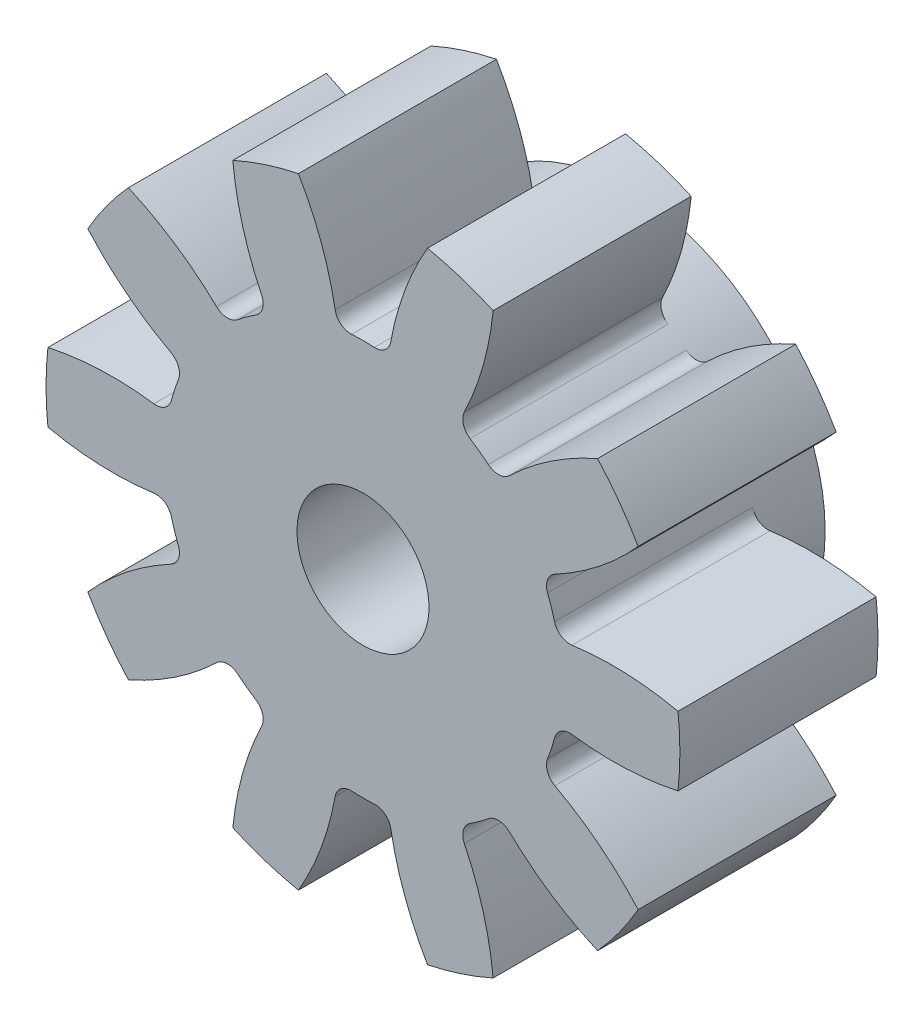
SolidWorks part; units mm, degrees
ref_plane "Front Plane" through (0, 0, 0) normal (0, 0, 1) x (1, 0, 0)
ref_plane "Top Plane" through (0, 0, 0) normal (0, 1, 0) x (1, 0, 0)
ref_plane "Right Plane" through (0, 0, 0) normal (1, 0, 0) x (0, 0, -1)
sketch "Sketch1" plane through (0, 0, 0) normal (0, 0, 1) x (1, 0, 0)
  circle A0 centre (0, 0) radius 10
  circle A1 centre (0, 0) radius 12
  circle A2 centre (0, 0) radius 7.5
  dimension "D1" = 20
  dimension "D2" = 24
  dimension "D3" = 4.5
extrude "Boss-Extrude1" add sketch "Sketch1" along normal mid plane 425 contours A1
sketch "Sketch2" plane through (0, 0, 0) normal (0, 0, 1) x (1, 0, 0)
  line L0 (0, 0) -> (0, 12) construction
  line L1 (-1.5643, 9.8769) -> (1.5643, 9.8769) construction
  line L2 (-0.9691, 7.4371) -> (0, 0) construction
  line L3 (0, 5.5789) -> (-2.6051, 12.7363) construction
  line L4 (0, 0) -> (3.7082, 11.4127) construction
  line L5 (1.5643, 9.8769) -> (4.5399, 8.9101) construction
  circle A0 centre (0, 0) radius 12 construction
  arc A1 (-3.0254, 12.6431) -> (-0.9691, 7.4371) centre (-12.3373, 5.9558) cw
  arc A2 (3.0254, 12.6431) -> (0.9691, 7.4371) centre (12.3373, 5.9558) ccw
  circle A3 centre (0, 0) radius 7.5 construction
  arc A4 (0.9691, 7.4371) -> (-0.9691, 7.4371) centre (0, 0) ccw
  circle A5 centre (0, 0) radius 12 construction
  circle A6 centre (0, 0) radius 10 construction
  circle A7 centre (0, 0) radius 13
  arc A8 (3.0254, 12.6431) -> (-3.0254, 12.6431) centre (0, 0) ccw
  dimension "D2" = 1.9081
  dimension "D3" = 20
  dimension "D4" = 18
extrude "Cut-Extrude1" cut sketch "Sketch2" against normal through all both and the other way through all
fillet "Fillet1" radius 0.6 1 edges at (-0.9691, 7.4371, 0) type face fillet first side face at (-1.5984, 9.6298, 0) second side face at (0, 7.4686, 0)
fillet "Fillet2" radius 0.6 1 edges at (0.9691, 7.4371, 0) type face fillet first side face at (1.5984, 9.6298, 0) second side face at (0.2709, 7.4788, 0)
sketch "Sketch3" plane through (0, 0, -212.5) normal (0, 0, -1) x (-1, 0, 0)
pattern_circular "CirPattern2" count 10 over 360 about axis through (0, 0, 212.5) along (0, 0, 1) of "Cut-Extrude1", "Fillet1", "Fillet2"
sketch "Sketch4" plane through (0, 0, -212.5) normal (0, 0, -1) x (-1, 0, 0)
  circle A0 centre (0, 0) radius 7.5
  circle A1 centre (0, 0) radius 2.5
  dimension "D1" = 5
extrude "Boss-Extrude2" add sketch "Sketch4" along normal mid plane 5 contours A0 | A1
sketch "Sketch5" plane through (0, 0, -212.5) normal (0, 0, -1) x (-1, 0, 0)
  circle A0 centre (0, 0) radius 3
extrude "Cut-Extrude2" cut sketch "Sketch5" against normal blind 32 and the other way through all
sketch "Sketch6" plane through (0, 0, 212.5) normal (0, 0, 1) x (1, 0, 0)
  circle A0 centre (0, 0) radius 7.5
  dimension "D1" = 15
extrude "Boss-Extrude3" add sketch "Sketch6" along normal mid plane 12
ref_plane "Plane1" through (0, 0, -205) normal (0, 0, -1) x (-1, 0, 0)
sketch "Sketch7" plane through (0, 0, 218.5) normal (0, 0, 1) x (1, 0, 0)
  circle A0 centre (0, 0) radius 12
extrude "Cut-Extrude3" cut sketch "Sketch7" against normal up to surface (423.5 mm away) contours A0 up to plane "Plane1"
sketch "Sketch8" plane through (0, 0, -215) normal (0, 0, -1) x (-1, 0, 0)
  circle A0 centre (0, 0) radius 1.65
  circle A1 centre (0, 0) radius 7.5
  dimension "D1" = 3.3
extrude "Boss-Extrude4" add sketch "Sketch8" against normal up to surface (10 mm away) up to face at (-3, 0, -205)
sketch "Sketch9" plane through (0, 0, -224.2059) normal (0, 0, -1) x (-1, 0, 0)
  circle A0 centre (0, 0) radius 2.5
  dimension "D1" = 5
extrude "Cut-Extrude4" cut sketch "Sketch9" against normal through all contours A0
equation "\"Module\"= 2mm"
equation "\"Number of Teeth\"= 10"
equation "\"D1@Sketch1\"=\"Module\" * \"Number of Teeth\""
equation "\"D2@Sketch1\"=(\"Number of Teeth\" + 2) * \"Module\""
equation "\"D3@Sketch1\"=\"Module\" * if( \"Module\" = > 1.25, 2.25, 2.4)"
equation "\"D4@Sketch2\"=180 / \"Number of Teeth\""
equation "\"D1@Fillet1\"=0.3 * \"Module\""
